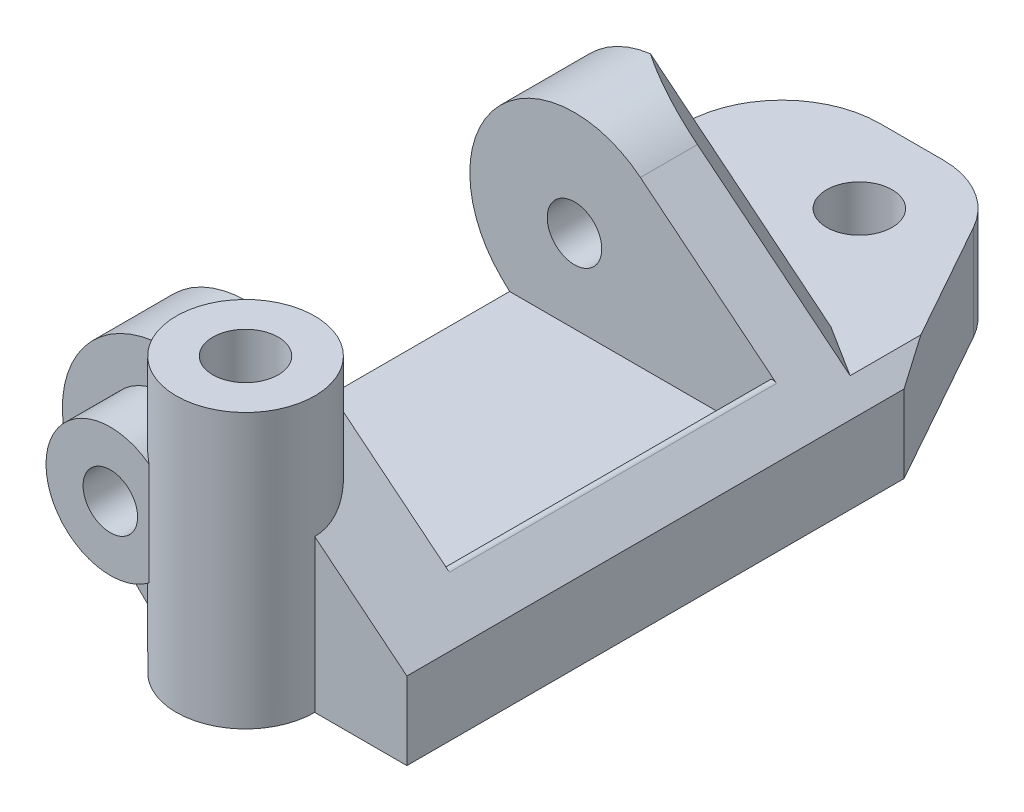
SolidWorks part; units mm, degrees
ref_plane "Front Plane" through (0, 0, 0) normal (0, 0, 1) x (1, 0, 0)
ref_plane "Top Plane" through (0, 0, 0) normal (0, 1, 0) x (1, 0, 0)
ref_plane "Right Plane" through (0, 0, 0) normal (1, 0, 0) x (0, 0, -1)
sketch "Sketch2" plane through (0, 0, 0) normal (0, 1, 0) x (1, 0, 0)
  line L0 (-5.7, 6.8) -> (-9.1, 6.8)
  line L1 (-5.7, -16) -> (5.7, -16)
  line L2 (-5.7, -16) -> (-5.7, 16)
  line L3 (-5.7, 16) -> (5.7, 16)
  line L4 (5.7, -16) -> (5.7, 16)
  line L5 (-5.7, -16) -> (5.7, 16) construction
  line L6 (-5.7, 16) -> (5.7, -16) construction
  line L7 (-9.1, 6.8) -> (-9.1, 11.5)
  line L8 (-4.6, 16) -> (-5.7, 16)
  line L9 (5.7, 6.8) -> (1.6608, 14.0281)
  arc A0 (-9.1, 11.5) -> (-4.6, 16) centre (-4.6, 11.5) cw
  arc A1 (1.6608, 14.0281) -> (-1.7, 16) centre (-1.7, 12.15) ccw
  circle A2 centre (-1.7, -16) radius 3.175
  point P0 (0, 0)
  dimension "D1" = 4.5
  dimension "D7" = 6.35
  dimension "D2" = 32
  dimension "D3" = 11.4
  dimension "D4" = 14.8
  dimension "D5" = 9.2
  dimension "D6" = 28.15
  dimension "D8" = 7.4
extrude "Boss-Extrude1" add sketch "Sketch2" along normal blind 4.35 contours L1 A2 | A2 L1 L4 L9 A1 L3 A0 L2 | L1 A2 | A0 L7 L0 L2 region at (-0.2076, 0, 0.27) region at (-7.2845, 0, -10.8295) region at (-1.7, 0, 14.6525) region at (-1.7, 0, 17.3475)
sketch "Sketch3" plane through (0, 0, 16) normal (0, 0, 1) x (1, 0, 0)
  line L0 (-5.7, 4.35) -> (-8.6425, 1.4949)
  line L1 (5.7, 0.79) -> (-2.2768, -5.6783)
  line L2 (5.7, 4.35) -> (5.7, 0) construction
  line L3 (1.475, 4.35) -> (5.7, 4.35) construction
  line L4 (1.475, 4.35) -> (-4.875, 4.35) construction
  line L5 (-5.7, 4.35) -> (5.7, 0.79)
  circle A0 centre (-5.3, -1.95) radius 4.8
  point P15 (-10.1, -1.95)
  line M4 (-5.7, 0) -> (-4.875, 0)
  line M5 (-4.875, 0) -> (-4.875, 4.35)
  line M7 (-5.7, 4.35) -> (-5.7, 0)
  dimension "D3" = 9.6
  dimension "D1" = 3.56
  dimension "D2" = 15.8
  dimension "D4" = 6.3
extrude "Boss-Extrude2" add sketch "Sketch3" against normal up to surface (22.8 mm away) contours A0 L1 L5 M5 | A0 M7 M5 M4 | A0 M5 M7 M4 | A0 L5 M5 M7 | A0 L0 M7 region at (-6.4799, 3.1271, 16) region at (-5.3003, 3.5346, 16) region at (-5.3004, -2.063, 16) region at (0.5611, 0.2898, 16) region at (-5.2876, 1.422, 16) up to face at (-7.4, 2.175, -6.8)
sketch "Sketch4" plane through (0, 0, 16) normal (0, 0, 1) x (1, 0, 0)
  line L0 (4.7258, 0) -> (-2.2768, -5.6783) construction
  line L1 (4.7258, 0) -> (5.7, 0) construction
  line L2 (5.7, 4.35) -> (5.7, 0) construction
  line L3 (5.7, 0.79) -> (4.7258, 0)
  line L4 (4.7258, 0) -> (5.7, 0)
  line L5 (5.7, 0.79) -> (5.7, 0)
  line M10 (4.7258, 0) -> (5.7, 0)
  line M11 (5.7, 0) -> (5.7, 4.35)
extrude "Cut-Extrude1" cut sketch "Sketch4" against normal through all contours L3 M11 M10 region at (5.3753, 0.2633, 16)
sketch "Sketch5" plane through (0, 4.35, 0) normal (0, 1, 0) x (1, 0, 0)
  circle A0 centre (-1.7, -16) radius 3.175
extrude "Boss-Extrude3" add sketch "Sketch5" against normal blind 12.57
sketch "Sketch6" plane through (0, 0, 16) normal (0, 0, 1) x (1, 0, 0)
  circle A0 centre (-5.3, -1.95) radius 2.95
  dimension "D1" = 5.9
extrude "Boss-Extrude4" add sketch "Sketch6" along normal offset from surface (2.6 mm away) 25.4 up to face at (-4.6789, -1.9331, -6.8)
chamfer "Chamfer1" distance 1.5 angle 45 1 edges at (1.2245, -2.8391, -6.8) tangent propagation no
sketch "Sketch7" plane through (0, 4.35, 0) normal (0, 1, 0) x (1, 0, 0)
  circle A0 centre (-1.7, 12.15) radius 1.5
  circle A1 centre (-1.7, -16) radius 1.5
  dimension "D1" = 3
extrude "Cut-Extrude2" cut sketch "Sketch7" against normal through all
sketch "Sketch8" plane through (0, 0, 18.6) normal (0, 0, 1) x (1, 0, 0)
  circle A0 centre (-5.3, -1.95) radius 1.25
  dimension "D1" = 2.5
extrude "Cut-Extrude3" cut sketch "Sketch8" against normal through all
ref_plane "Plane1" through (3.7, 0, 0) normal (1, 0, 0) x (0, 0, -1)
sketch "Sketch9" plane through (3.7, 0, 0) normal (1, 0, 0) x (0, 0, -1)
  line L0 (-16, -6.75) -> (6.3717, -6.75) construction
  line L1 (-12.3141, 1.85) -> (2.6859, 1.85)
  line L2 (-12.3141, 1.85) -> (-12.3141, -6.75)
  line L3 (-12.3141, -6.75) -> (2.6859, -6.75)
  line L4 (2.6859, 1.85) -> (2.6859, -6.75)
  line L5 (-12.3141, 1.85) -> (2.6859, -6.75) construction
  line L6 (-12.3141, -6.75) -> (2.6859, 1.85) construction
  line L7 (-16, 4.35) -> (6.8, 4.35) construction
  point P0 (-4.8141, -2.45)
  point P11 (-4.8141, -6.75)
  dimension "D1" = 15
  dimension "D2" = 2.5
extrude "Cut-Extrude4" cut sketch "Sketch9" against normal blind 25.4
chamfer "Chamfer2" distance 2.5 angle 45 1 edges at (3.7, 1.85, 4.8141)
fillet "Fillet1" radius 0.25 1 edges at (3.7, -0.8318, 4.8141)
ref_plane "Plane2" through (0, 0, 4.8141) normal (0, 0, 1) x (1, 0, 0)
mirror "Mirror1" about plane through (0, 4.35, 0) normal (0, 1, 0) of bodies 108
delete or keep bodies "Body-Delete/Keep 1" type keep bodies bodies 109
